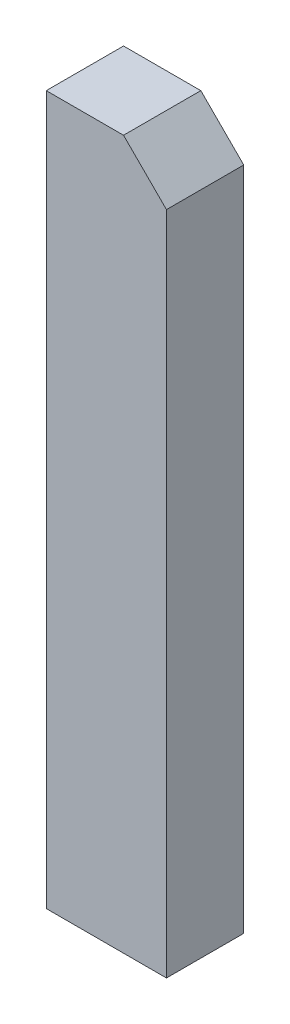
SolidWorks part; units mm, degrees
ref_plane "Front Plane" through (0, 0, 0) normal (0, 0, 1) x (1, 0, 0)
ref_plane "Top Plane" through (0, 0, 0) normal (0, 1, 0) x (1, 0, 0)
ref_plane "Right Plane" through (0, 0, 0) normal (1, 0, 0) x (0, 0, -1)
sketch "Sketch2" plane through (0, 0, 0) normal (0, 1, 0) x (1, 0, 0)
  line L1 (-1.4, -0.9) -> (1.4, -0.9)
  line L2 (-1.4, -0.9) -> (-1.4, 0.9)
  line L3 (-1.4, 0.9) -> (1.4, 0.9)
  line L4 (1.4, -0.9) -> (1.4, 0.9)
  line L5 (-1.4, -0.9) -> (1.4, 0.9) construction
  line L6 (-1.4, 0.9) -> (1.4, -0.9) construction
  point P0 (0, 0)
  dimension "D1" = 1.8
  dimension "D2" = 2.8
extrude "Boss-Extrude1" add sketch "Sketch2" along normal blind 16.5
chamfer "Chamfer1" distance 1 angle 45 1 edges at (1.4, 16.5, 0)
